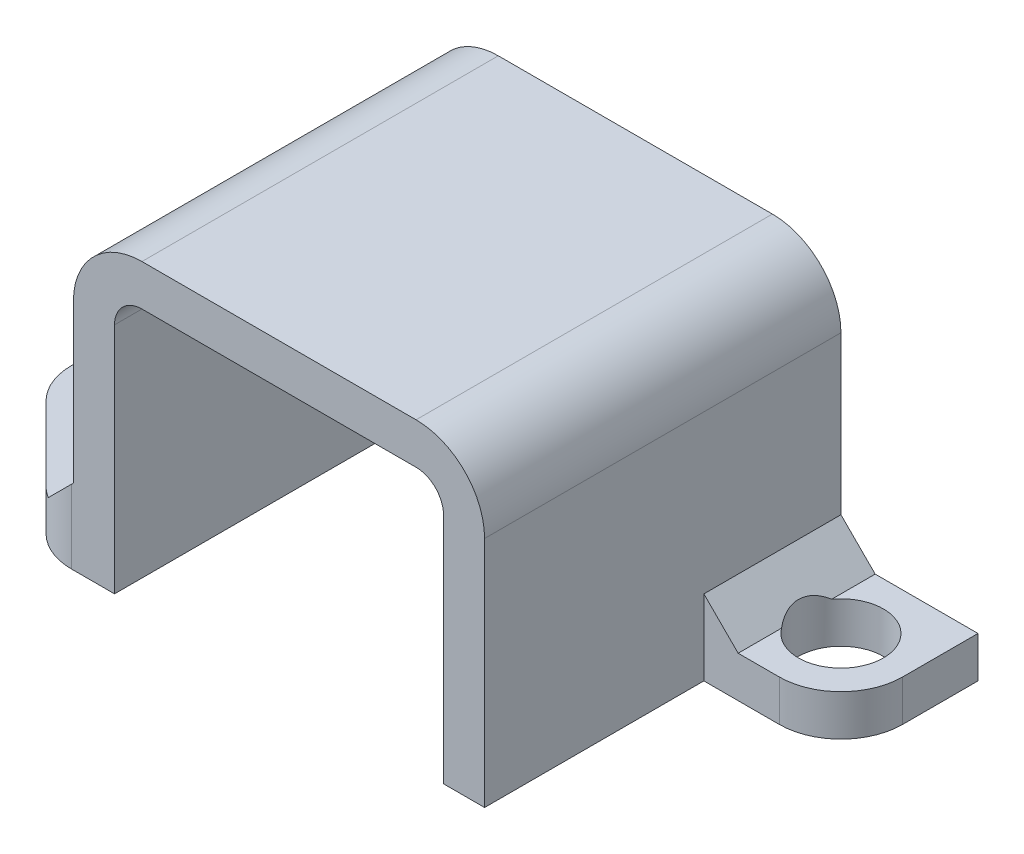
SolidWorks part; units mm, degrees
ref_plane "Front Plane" through (0, 0, 0) normal (0, 0, 1) x (1, 0, 0)
ref_plane "Top Plane" through (0, 0, 0) normal (0, 1, 0) x (1, 0, 0)
ref_plane "Right Plane" through (0, 0, 0) normal (1, 0, 0) x (0, 0, -1)
sketch "Sketch1" plane through (0, 0, 0) normal (0, 0, 1) x (1, 0, 0)
  line L0 (0, 1.5) -> (0, -9.7234) construction
  line L1 (6, 0) -> (-6, 0)
  line L2 (-6, 0) -> (-6, -9.5)
  line L3 (-6, -9.5) -> (-12.5, -9.5)
  line L4 (-12.5, -9.5) -> (-12.5, -8)
  line L5 (-12.5, -8) -> (-7.5, -8)
  line L6 (-7.5, -8) -> (-7.5, 1.5)
  line L7 (-7.5, 1.5) -> (7.5, 1.5)
  line L8 (12.5, -9.5) -> (12.5, -8)
  line L9 (12.5, -8) -> (7.5, -8)
  line L10 (6, -9.5) -> (12.5, -9.5)
  line L11 (6, 0) -> (6, -9.5)
  line L12 (7.5, -8) -> (7.5, 1.5)
  point P9 (-9.25, -9.5)
  point P17 (0, 0)
  dimension "D1" = 9.5
  dimension "D2" = 12
  dimension "D3" = 1.5
  dimension "D4" = 1.5
  dimension "D5" = 5
  dimension "D6" = 1.5
extrude "Boss-Extrude1" add sketch "Sketch1" along normal blind 13
sketch "Sketch2" plane through (0, -8, 0) normal (0, 1, 0) x (1, 0, 0)
  line L0 (7.5, -13) -> (7.5, 0) construction
  line L1 (12.5, -13) -> (7.5, -13)
  line L2 (12.5, -13) -> (12.5, -5)
  line L3 (12.5, -5) -> (7.5, -5)
  line L4 (7.5, -13) -> (7.5, -5)
  line L5 (12.5, 0) -> (7.5, 0) construction
  dimension "D1" = 5
extrude "Cut-Extrude1" cut sketch "Sketch2" against normal through all
sketch "Sketch3" plane through (0, -8, 0) normal (0, 1, 0) x (1, 0, 0)
  line L0 (12.5, -2.5) -> (-12.5, -2.5) construction
  line L1 (12.5, -5) -> (12.5, 0) construction
  line L2 (-12.5, -13) -> (-12.5, 0) construction
  circle A0 centre (10, -2.5) radius 1.55
  circle A1 centre (-10, -2.5) radius 1.55
  dimension "D1" = 3.1
  dimension "D2" = 2.5
  dimension "D3" = 3.1
  dimension "D4" = 2.5
extrude "Cut-Extrude2" cut sketch "Sketch3" against normal through all
fillet "Fillet1" radius 1 2 edges at (-6, 0, 6.5) (6, 0, 6.5)
fillet "Fillet2" radius 2.5 2 edges at (-7.5, 1.5, 6.5) (7.5, 1.5, 6.5)
chamfer "Chamfer1" distance 4 angle 45 1 edges at (-12.5, -8.75, 13)
fillet "Fillet3" radius 2.25 2 edges at (-12.5, -8.75, 9) (-8.5, -8.75, 13)
fillet "Fillet4" radius 2.25 1 edges at (12.5, -8.75, 5)
chamfer "Chamfer2" distance 1.25 angle 45 2 edges at (-7.5, -8, 6.5) (7.5, -8, 2.5)
